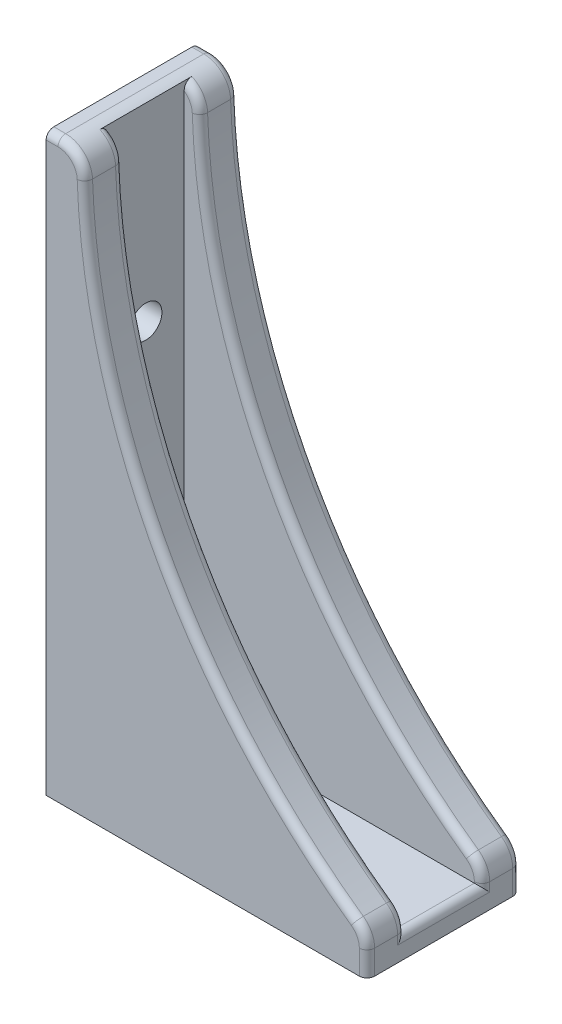
SolidWorks part; units mm, degrees
ref_plane "Front Plane" through (0, 0, 0) normal (0, 0, 1) x (1, 0, 0)
ref_plane "Top Plane" through (0, 0, 0) normal (0, 1, 0) x (1, 0, 0)
ref_plane "Right Plane" through (0, 0, 0) normal (1, 0, 0) x (0, 0, -1)
sketch "Sketch1" plane through (0, 0, 0) normal (0, 0, 1) x (1, 0, 0)
  line L0 (11.8365, 5) -> (11.8365, 0)
  line L1 (0, 0) -> (41.8365, 0)
  line L2 (0, 0) -> (0, 75)
  line L3 (0, 75) -> (41.8365, 75)
  line L4 (41.8365, 0) -> (41.8365, 75)
  line L5 (41.8365, 75) -> (5, 75)
  line L6 (41.8365, 75) -> (41.8365, 5)
  line L7 (41.8365, 5) -> (5, 5)
  line L8 (5, 75) -> (5, 5)
  line L9 (41.8365, 75) -> (3, 75)
  line L10 (41.8365, 75) -> (41.8365, 3)
  line L11 (41.8365, 3) -> (3, 3)
  line L12 (3, 75) -> (3, 3)
  dimension "D1" = 30
  dimension "D2" = 2
  dimension "D3" = 2
  dimension "D4" = 3
  dimension "D5" = 3
  dimension "D6" = 75
  dimension "D7" = 11.8365
extrude "Boss-Extrude1" add sketch "Sketch1" along normal blind 20 contours L12 L3 L2 L1 L4 L11 | L3 L12 L11 L4 L7 L8 | L11 L4 L7 L0 | L4 L11 L0 L1 region at (26.8365, 4, 0) region at (4.3831, 35.9649, 0) region at (26.8365, 1.5, 0) region at (2.1238, 33.7055, 0)
extrude "Cut-Extrude1" cut sketch "Sketch1<3>" along normal offset from surface (15 mm away) 5 contours L3 L12 L11 L4 L7 L8 | L11 L4 L7 L0 region at (26.8365, 4, 0) region at (4.3831, 35.9649, 0) up to face at (15.6122, 26.6667, 20)
sketch "Sketch1<3>" plane through (0, 0, 0) normal (0, 0, 1) x (1, 0, 0) same geometry as "Sketch1"
extrude "Boss-Extrude2" add sketch "Sketch1<4>" along normal blind 5 contours L3 L12 L11 L4 L7 L8 | L11 L4 L7 L0 region at (26.8365, 4, 0) region at (4.3831, 35.9649, 0)
sketch "Sketch1<4>" plane through (0, 0, 0) normal (0, 0, 1) x (1, 0, 0) same geometry as "Sketch1"
sketch "Sketch2" plane through (0, 0, 0) normal (0, -1, 0) x (1, 0, 0)
  line L0 (3, 15) -> (3, 5) construction
  line L1 (0, 20) -> (0, 0) construction
  circle A0 centre (11.8365, 10) radius 2.1
  point P2 (0, 0)
  point P5 (3, 10)
  dimension "D1" = 4.2
  dimension "D2" = 11.8365
extrude "Cut-Extrude2" cut sketch "Sketch2" against normal up to next
sketch "Sketch3" plane through (0, 0, 0) normal (-1, 0, 0) x (0, 0, 1)
  line L0 (15, 3) -> (5, 3) construction
  line L1 (20, 0) -> (0, 0) construction
  circle A0 centre (10, 25) radius 2.1
  circle A1 centre (10, 50) radius 2.1
  point P4 (0, 0)
  point P7 (10, 3)
  dimension "D1" = 4.2
  dimension "D2" = 25
  dimension "D3" = 25
extrude "Cut-Extrude3" cut sketch "Sketch3" against normal up to next
fillet "Fillet2" radius 84 2 edges at (5, 5, 17.5) (5, 5, 2.5)
fillet "Fillet3" radius 3.5 4 edges at (5, 75, 2.5) (41.8365, 5, 2.5) (41.8365, 5, 17.5) (3, 3, 10)
fillet "Fillet4" radius 1 19 edges at (0.7759, 75, 0) (3.9837, 74.0171, 0) (41.8365, 1.5846, 0) (41.4464, 4.7751, 0) (41.8365, 1.5846, 20) (41.4464, 4.7751, 20) (0.7759, 75, 20) (3.9837, 74.0171, 20) (4.4614, 73.4452, 15) (41.8365, 3.0846, 15) (41.4464, 4.7751, 15) (41.8365, 3.0846, 5) (41.4464, 4.7751, 5) (4.4614, 73.4452, 5) (15.0365, 34.6927, 0) (15.0365, 34.6927, 20) (41.8365, 3, 10) (15.0365, 34.6927, 15) (15.0365, 34.6927, 5)
